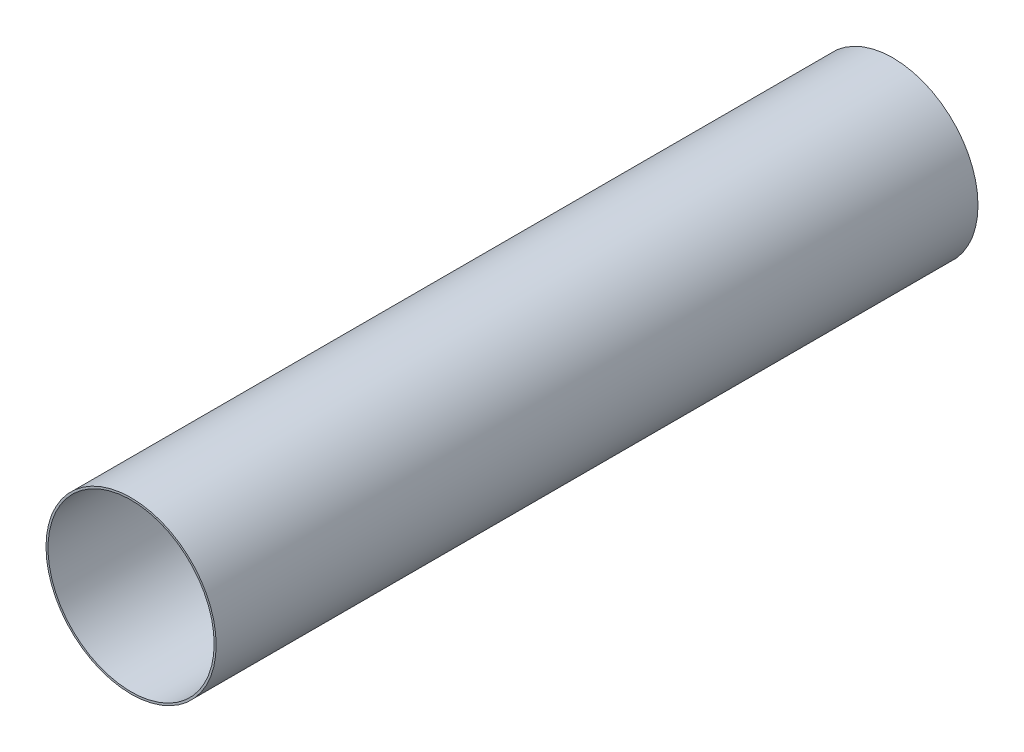
SolidWorks part; units mm, degrees
material "Thornel Mat VMA"
ref_plane "Front Plane" through (0, 0, 0) normal (0, 0, 1) x (1, 0, 0)
ref_plane "Top Plane" through (0, 0, 0) normal (0, 1, 0) x (1, 0, 0)
ref_plane "Right Plane" through (0, 0, 0) normal (1, 0, 0) x (0, 0, -1)
sketch "Sketch1" plane through (0, 0, 0) normal (0, 0, 1) x (1, 0, 0)
  circle A0 centre (0, 0) radius 85.0999
  circle A1 centre (0, 0) radius 83.0999
  dimension "D1" = 166.1998
  dimension "D2" = 170.1998
extrude "Boss-Extrude1" add sketch "Sketch1" along normal mid plane 762
equation "\"TubeDiameter\" = 6.5433in"
equation "\"D1@Sketch1\"=\"TubeDiameter\""
equation "\"D2@Sketch1\"=\"TubeDiameter\"+4mm"
